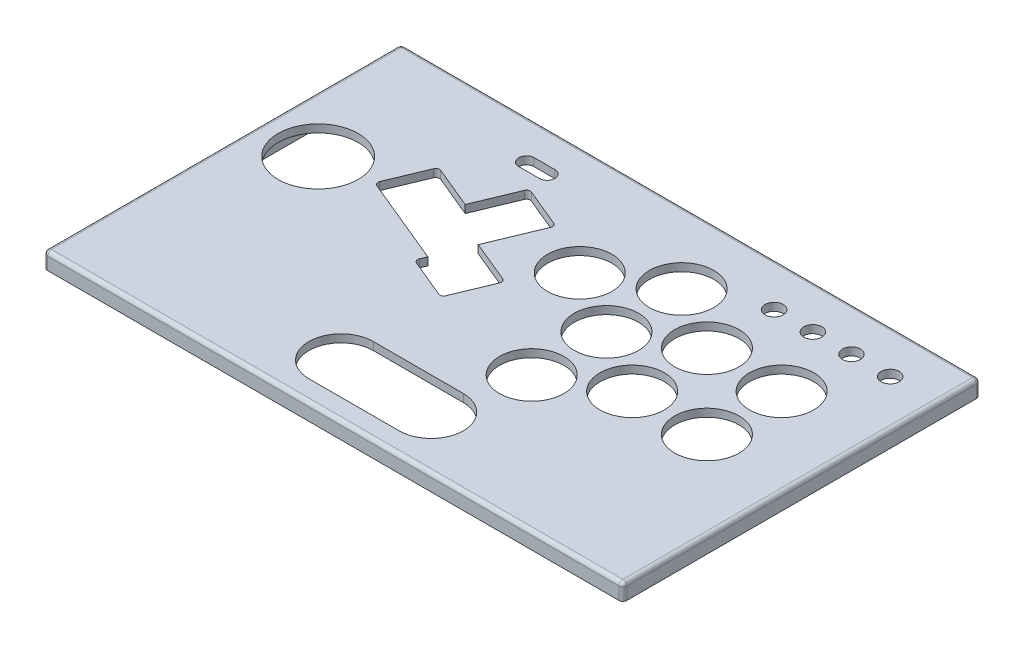
SolidWorks part; units mm, degrees
ref_plane "Front Plane" through (0, 0, 0) normal (0, 0, 1) x (1, 0, 0)
ref_plane "Top Plane" through (0, 0, 0) normal (0, 1, 0) x (1, 0, 0)
ref_plane "Right Plane" through (0, 0, 0) normal (1, 0, 0) x (0, 0, -1)
sketch "Button Cutouts" plane through (0, 0, 0) normal (0, 1, 0) x (1, 0, 0)
  line L0 (24.5, 61) -> (24.5, 32) construction
  line L1 (298.8548, 529.5585) -> (1494.2739, 529.5585) construction
  line L12 (-36.2591, 48.1292) -> (-29.3708, 64.7591) construction
  line L20 (49.5, 75) -> (49.5, 46) construction
  line L21 (78.5, 75) -> (78.5, 46) construction
  line L22 (17.5, 0) -> (-17.5, 0) construction
  line L28 (-36.2591, 48.1292) -> (-19.6292, 41.2409) construction
  line L29 (17.5, -12.5) -> (-17.5, -12.5)
  line L30 (17.5, 12.5) -> (-17.5, 12.5)
  line L31 (24.6803, 89.9994) -> (49.5, 75) construction
  line L32 (24.6803, 89.9994) -> (24.5, 61) construction
  line L33 (-0.5241, 75.6559) -> (24.6803, 89.9994) construction
  line L34 (-0.5241, 75.6559) -> (24.5, 61) construction
  line L48 (-29.3708, 64.7591) -> (-12.7409, 57.8708) construction
  line L49 (-19.6292, 41.2409) -> (-12.7409, 57.8708) construction
  line L50 (-36.2591, 48.1292) -> (-12.7409, 57.8708) construction
  line L51 (-29.3708, 64.7591) -> (-19.6292, 41.2409) construction
  line L52 (-35.6984, 52.2266) -> (-28.8101, 68.8564) construction
  line L53 (-35.6984, 52.2266) -> (-52.3282, 59.1149) construction
  line L54 (-28.8101, 68.8564) -> (-45.4399, 75.7447) construction
  line L55 (-52.3282, 59.1149) -> (-45.4399, 75.7447) construction
  line L56 (-35.6984, 52.2266) -> (-45.4399, 75.7447) construction
  line L57 (-28.8101, 68.8564) -> (-52.3282, 59.1149) construction
  line L58 (-69.9281, 66.405) -> (-63.0398, 83.0348) construction
  line L59 (-69.9281, 66.405) -> (-53.2983, 59.5167) construction
  line L60 (-63.0398, 83.0348) -> (-46.41, 76.1465) construction
  line L61 (-53.2983, 59.5167) -> (-46.41, 76.1465) construction
  line L62 (-69.9281, 66.405) -> (-46.41, 76.1465) construction
  line L63 (-63.0398, 83.0348) -> (-53.2983, 59.5167) construction
  line L64 (-40.5692, 63.9856) -> (-22.9693, 56.6955) construction
  line L65 (-40.5692, 63.9856) -> (-58.1691, 71.2758) construction
  line L66 (-45.0381, 76.7148) -> (-38.1498, 93.3446) construction
  line L67 (-45.0381, 76.7148) -> (-28.4083, 69.8265) construction
  line L68 (-38.1498, 93.3446) -> (-21.52, 86.4563) construction
  line L69 (-28.4083, 69.8265) -> (-21.52, 86.4563) construction
  line L70 (-45.0381, 76.7148) -> (-21.52, 86.4563) construction
  line L71 (-38.1498, 93.3446) -> (-28.4083, 69.8265) construction
  line L72 (-40.5692, 63.9856) -> (-33.2791, 81.5855) construction
  line L73 (-24.5, 53) -> (-22.9693, 56.6955) construction
  line L74 (-58.1691, 71.2758) -> (-65.4592, 53.6759) construction
  line L75 (-65.4592, 53.6759) -> (-90.4039, 64.0083) construction
  line L76 (-70.5814, 66.1344) -> (-63.3104, 83.6881)
  line L77 (-63.3104, 83.6881) -> (-45.7105, 76.398)
  line L78 (-45.7105, 76.398) -> (-38.4204, 93.9979)
  line L79 (-38.4204, 93.9979) -> (-20.8667, 86.7269)
  line L80 (-20.8667, 86.7269) -> (-29.6876, 65.4315)
  line L81 (-29.6876, 65.4315) -> (-12.0877, 58.1414)
  line L82 (-12.0877, 58.1414) -> (-19.3586, 40.5877)
  line L83 (-19.3586, 40.5877) -> (-36.9123, 47.8586)
  line L84 (-36.9123, 47.8586) -> (-35.3816, 51.5542)
  line L85 (-35.3816, 51.5542) -> (-70.5814, 66.1344)
  line L86 (-66.484, 74.7199) -> (-66.9459, 74.9112) construction
  line L87 (-29.6436, 90.3624) -> (-29.8349, 89.9005) construction
  line L88 (-16.1851, 49.5558) -> (-15.7231, 49.3645) construction
  line L89 (-33.2791, 140.3317) -> (-33.2791, 81.5855) construction
  circle A0 centre (24.5, 32) radius 12.5
  circle A1 centre (24.5, 61) radius 12.5
  circle A2 centre (49.5, 46) radius 12.5
  circle A3 centre (49.5, 75) radius 12.5
  circle A4 centre (78.5, 75) radius 12.5
  circle A5 centre (78.5, 46) radius 12.5
  arc A8 (17.5, -12.5) -> (17.5, 12.5) centre (17.5, 0) ccw
  arc A9 (-17.5, 12.5) -> (-17.5, -12.5) centre (-17.5, 0) ccw
  circle A10 centre (-90.4039, 64.0083) radius 15.5
  circle A11 centre (24.6803, 89.9994) radius 12.5
  circle A12 centre (-0.5241, 75.6559) radius 12.5
  point P1 (-24.5, 53)
  point P5 (-40.5692, 63.9856)
  point P6 (-58.1691, 71.2758)
  point P37 (0, 0)
  point P45 (-33.2791, 81.5855)
  point P54 (-30, 0)
  point P55 (30, 0)
  dimension "D2" = 25
  dimension "D12" = 12.5
  dimension "D18" = 31
  dimension "D25" = 22.5
  dimension "D1" = 29
  dimension "D3" = 25
  dimension "D4" = 29
  dimension "D5" = 14
  dimension "D6" = 18
  dimension "D7" = 19.05
  dimension "D8" = 53
  dimension "D9" = 7
  dimension "D10" = 4
  dimension "D11" = 27
  dimension "D13" = 32
  dimension "D14" = 7
  dimension "D15" = 19.05
  dimension "D16" = 0.5
  dimension "D17" = 60
  dimension "D19" = 0.5
  dimension "D20" = 0.5
  dimension "D21" = 29
  dimension "D22" = 29
  dimension "D23" = 0.5
  dimension "D24" = 0.5
sketch "Sketch2" plane through (0, 0, 0) normal (0, 1, 0) x (1, 0, 0)
  line L0 (-105.9039, 64.0083) -> (-112.4039, 64.0083) construction
  line L1 (-112.4039, 118.1994) -> (112.4039, 118.1994)
  line L2 (-112.4039, 118.1994) -> (-112.4039, -20.5)
  line L3 (-112.4039, -20.5) -> (112.4039, -20.5)
  line L4 (112.4039, 118.1994) -> (112.4039, -20.5)
  line L5 (24.6803, 102.4994) -> (24.6803, 118.1994) construction
  line L6 (0, -12.5) -> (0, -20.5) construction
  line L7 (17.5, -12.5) -> (-17.5, -12.5) construction
  circle A0 centre (-90.4039, 64.0083) radius 15.5 construction
  circle A2 centre (24.6803, 89.9994) radius 12.5 construction
  point P4 (0, -20.5)
  dimension "D2" = 6.5
  dimension "D1" = 8
  dimension "D3" = 15.7
extrude "top plate" add sketch "Sketch2" along normal blind 6.35
extrude "primary button cutouts" cut sketch "Button Cutouts" along normal up to next
fillet "Fillet1" radius 1.5 7 edges at (-20.8667, 3.175, -86.7269) (-12.0877, 3.175, -58.1414) (-19.3586, 3.175, -40.5877) (-36.9123, 3.175, -47.8586) (-70.5814, 3.175, -66.1344) (-63.3104, 3.175, -83.6881) (-38.4204, 3.175, -93.9979)
sketch "Sketch4" plane through (0, 0, 0) normal (0, -1, 0) x (1, 0, 0)
  line L0 (112.4039, 20.5) -> (112.4039, -118.1994) construction
  line L1 (-106.4039, 14.5) -> (106.4039, 14.5)
  line L2 (-106.4039, 14.5) -> (-106.4039, -112.1994)
  line L3 (-106.4039, -112.1994) -> (106.4039, -112.1994)
  line L4 (106.4039, 14.5) -> (106.4039, -112.1994)
  line L5 (-112.4039, 20.5) -> (112.4039, 20.5) construction
  line L6 (112.4039, -118.1994) -> (-112.4039, -118.1994) construction
  line L7 (-112.4039, -118.1994) -> (-112.4039, 20.5) construction
  dimension "D1" = 6
  dimension "D2" = 6
  dimension "D3" = 6
  dimension "D4" = 6
extrude "Cut-Extrude2" cut sketch "Sketch4" against normal blind 3.3
fillet "Fillet2" radius 1.5 8 edges at (112.4039, 3.175, -118.1994) (-112.4039, 3.175, -118.1994) (-112.4039, 3.175, 20.5) (112.4039, 3.175, 20.5) (112.4039, 6.35, -48.8497) (0, 6.35, -118.1994) (0, 6.35, 20.5) (-112.4039, 6.35, -48.8497)
sketch "Sketch5" plane through (0, 0, 0) normal (0, -1, 0) x (1, 0, 0)
  line L0 (110.9039, -118.1994) -> (-110.9039, -118.1994) construction
  line L1 (-91.4039, -112.1994) -> (-56.4039, -112.1994)
  line L2 (-91.4039, -112.1994) -> (-91.4039, -118.1994)
  line L3 (-91.4039, -118.1994) -> (-56.4039, -118.1994)
  line L4 (-56.4039, -112.1994) -> (-56.4039, -118.1994)
  line L5 (-56.4039, -112.1994) -> (-56.4039, -118.1994) construction
extrude "Cut-Extrude3" cut sketch "Sketch5" against normal blind 3
hole_wizard "Tap Drill for M3x0.5 Tap1" positions "3DSketch1" profile "Sketch6" hole size "M3x0.5" standard "ANSI Metric"
sketch3d "3DSketch1"
  line L0 (-108.4039, 0, 16.5) -> (-108.4039, 0, 20.5) construction
  line L1 (-110.9039, 0, 20.5) -> (110.9039, 0, 20.5) construction
  line L3 (-108.4039, 0, 16.5) -> (-112.4039, 0, 16.5)
  line L4 (-112.4039, 0, -116.6994) -> (-112.4039, 0, 19) construction
  line L6 (108.4039, 0, -114.1994) -> (112.4039, 0, -114.1994)
  line L7 (112.4039, 0, 19) -> (112.4039, 0, -116.6994) construction
  line L9 (108.4039, 0, -114.1994) -> (108.4039, 0, -118.1994)
  line L10 (110.9039, 0, -118.1994) -> (-56.4039, 0, -118.1994) construction
  point P0 (-108.4039, 0, 16.5)
  point P2 (-108.4039, 0, -114.1994)
  point P4 (108.4039, 0, -114.1994)
  point P6 (108.4039, 0, 16.5)
  dimension "D1" = 4
sketch "Sketch6" plane through (-108.4039, 0, 16.5) normal (1, 0, 0) x (0, 0, -1)
  line L0 (0, 0) -> (0, 4.7511)
  line L1 (0, 4.7511) -> (1.25, 4)
  line L2 (1.25, 4) -> (1.25, 0)
  line L5 (1.25, 0) -> (0, 0)
  line L10 (0, 4.7511) -> (-1.25, 4) construction
  line L11 (0, -6.35) -> (0, 107.95) construction
  dimension "Hole Dia." = 2.5
  dimension "Hole Depth" = 4
  dimension "Drill Angle" = 118
sketch "Sketch7" plane through (0, 6.35, 0) normal (0, 1, 0) x (1, 0, 0)
  line L0 (47.0909, 107.2568) -> (52.0946, 94.7583) construction
  line L1 (62.0909, 107.2613) -> (67.0946, 94.7628) construction
  line L2 (77.0909, 107.2658) -> (82.0946, 94.7673) construction
  line L3 (92.0909, 107.2703) -> (97.0946, 94.7718) construction
  circle A0 centre (49.5927, 101.0075) radius 3.5
  circle A1 centre (64.5927, 101.012) radius 3.5
  circle A2 centre (79.5927, 101.0166) radius 3.5
  circle A3 centre (94.5927, 101.0211) radius 3.5
  dimension "D1" = 7
extrude "extra_buttons" cut sketch "Sketch7" against normal up to next
sketch "Sketch8" plane through (0, 6.35, 0) normal (0, 1, 0) x (1, 0, 0)
  line L0 (-48.0625, 102.5336) -> (-40.0625, 102.5336) construction
  line L1 (-48.0625, 105.5336) -> (-40.0625, 105.5336)
  line L2 (-48.0625, 99.5336) -> (-40.0625, 99.5336)
  arc A0 (-48.0625, 105.5336) -> (-48.0625, 99.5336) centre (-48.0625, 102.5336) ccw
  arc A1 (-40.0625, 99.5336) -> (-40.0625, 105.5336) centre (-40.0625, 102.5336) ccw
  point P2 (-44.0625, 102.5336)
  point P7 (-38.5562, 102.8646)
  point P8 (-49.3478, 102.55)
  point P9 (-39.6134, 102.5875)
  point P10 (-48.674, 102.5924)
  point P11 (-44.0898, 102.5444)
  point P12 (-44.0625, 102.5336)
  point P13 (0, 0)
  dimension "D1" = 8
  dimension "D2" = 6
extrude "led_cutout" cut sketch "Sketch8" against normal up to next
